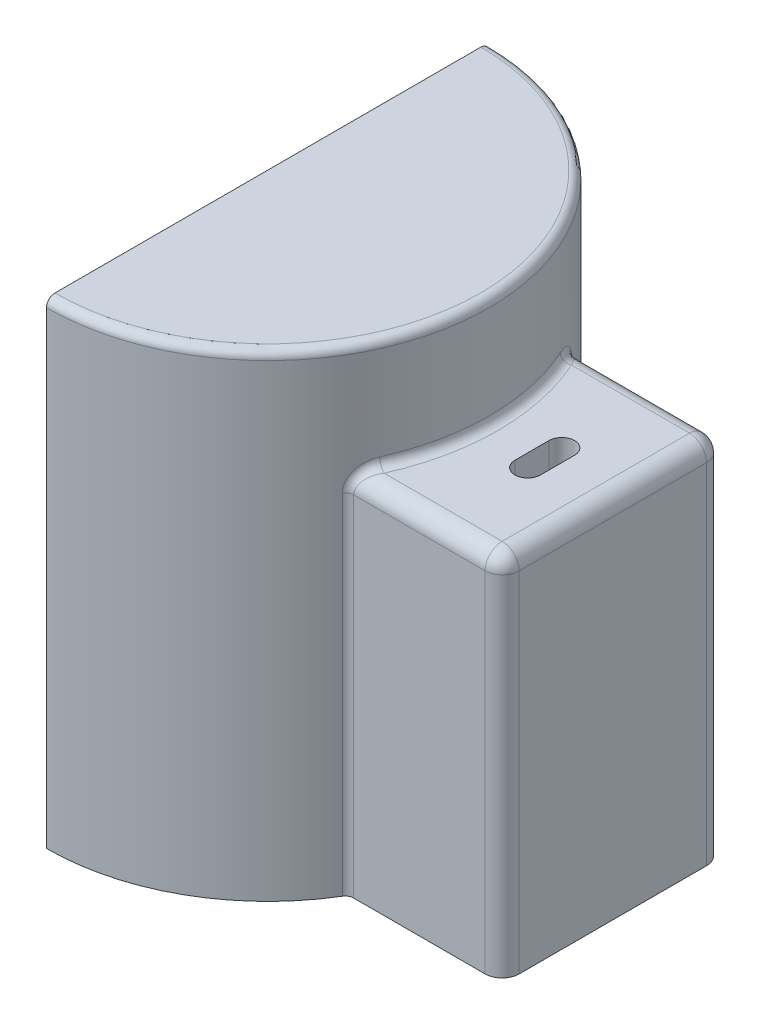
SolidWorks part; units mm, degrees
ref_plane "Спереди" through (0, 0, 0) normal (0, 0, 1) x (1, 0, 0)
ref_plane "Сверху" through (0, 0, 0) normal (0, 1, 0) x (1, 0, 0)
ref_plane "Справа" through (0, 0, 0) normal (1, 0, 0) x (0, 0, -1)
sketch "Эскиз1" plane through (0, 0, 0) normal (0, 1, 0) x (1, 0, 0)
  line L0 (0, 0) -> (0, 18805.5356) construction
  line L1 (0, 0) -> (-18805.5356, 0) construction
  line L2 (0, 26) -> (0, 23)
  line L3 (0, -23) -> (0, -26)
  line L4 (22.5167, 13) -> (40.5167, 13)
  line L5 (40.5167, 13) -> (40.5167, -13)
  line L6 (40.5167, -13) -> (22.5167, -13)
  line L7 (20.7123, -10) -> (37.5167, -10)
  line L8 (37.5167, -10) -> (37.5167, 10)
  line L9 (37.5167, 10) -> (20.7123, 10)
  arc A0 (0, -26) -> (24, -10) centre (0, 0) ccw
  arc A1 (0, -23) -> (20.7123, -10) centre (0, 0) ccw
  arc A2 (20.7123, 10) -> (0, 23) centre (0, 0) ccw
  arc A3 (24, 10) -> (0, 26) centre (0, 0) ccw
  dimension "D1" = 46
  dimension "D2" = 52
  dimension "D3" = 26
  dimension "D4" = 18
  dimension "D5" = 20
  dimension "D6" = 3
extrude "Бобышка-Вытянуть1" add sketch "Эскиз1" along normal blind 43 contours A1 L3 A0 L7 | A3 L9 L8 L7 A0 L6 L5 L4 | L9 A3 L2 A2 region at (12.632, 0, -19.4701) region at (31.5167, 0, -12.6838) region at (12.632, 0, 19.4701)
sketch "Эскиз2" plane through (0, 43, 0) normal (0, 1, 0) x (1, 0, 0)
  line L0 (0, 26) -> (0, 23)
  line L1 (0, -26) -> (0, -23)
  arc A0 (0, -26) -> (0, 26) centre (0, 0) ccw
  arc A1 (0, -23) -> (0, 23) centre (0, 0) ccw
extrude "Бобышка-Вытянуть2" add sketch "Эскиз2" along normal blind 13
sketch "Эскиз3" plane through (0, 56, 0) normal (0, 1, 0) x (1, 0, 0)
  line L0 (0, 26) -> (0, -26)
  arc A0 (0, -26) -> (0, 26) centre (0, 0) ccw
extrude "Бобышка-Вытянуть3" add sketch "Эскиз3" against normal blind 3
fillet "Скругление1" radius 1 5 edges at (22.5167, 21.5, 13) (22.5167, 21.5, -13) (37.5167, 21.5, -10) (37.5167, 21.5, 10) (26, 56, 0)
fillet "Скругление2" radius 2 2 edges at (40.5167, 21.5, -13) (40.5167, 21.5, 13)
sketch "Эскиз5" plane through (0, 43, 0) normal (0, 1, 0) x (1, 0, 0)
  line L3 (20.7123, 10) -> (37.5167, 10)
  line L4 (37.5167, 10) -> (37.5167, -10)
  line L5 (37.5167, -10) -> (20.7123, -10)
  line L6 (37.5167, -9) -> (37.5167, 9) construction
  arc A2 (20.7123, -10) -> (20.7123, 10) centre (0, 0) ccw
extrude "Бобышка-Вытянуть4" add sketch "Эскиз5" against normal blind 3
fillet "Скругление3" radius 1 5 edges at (28.6145, 40, 10) (37.2238, 40, 9.7071) (28.6145, 40, -10) (37.2238, 40, -9.7071) (37.5167, 40, 0)
fillet "Скругление4" radius 2 7 edges at (22.5961, 43, -13.1286) (30.8017, 43, -13) (39.9309, 43, -12.4142) (22.5961, 43, 13.1286) (30.8017, 43, 13) (39.9309, 43, 12.4142) (40.5167, 43, 0)
fillet "Скругление5" radius 1 3 edges at (22.7135, 42.197, 12.653) (22.7135, 42.197, -12.653) (26, 43, 0)
sketch "Эскиз6" plane through (0, 43, 0) normal (0, 1, 0) x (1, 0, 0)
  line L0 (32.5167, -2) -> (32.5167, 2) construction
  line L1 (31.0167, -2) -> (31.0167, 2)
  line L2 (34.0167, -2) -> (34.0167, 2)
  line L3 (38.5167, -11) -> (38.5167, 11) construction
  arc A0 (31.0167, -2) -> (34.0167, -2) centre (32.5167, -2) ccw
  arc A1 (34.0167, 2) -> (31.0167, 2) centre (32.5167, 2) ccw
  point P2 (32.5167, 0)
  point P10 (38.5167, 0)
  dimension "D1" = 1.5
  dimension "D2" = 4
  dimension "D3" = 6
extrude "Вырез-Вытянуть1" cut sketch "Эскиз6" against normal through all
